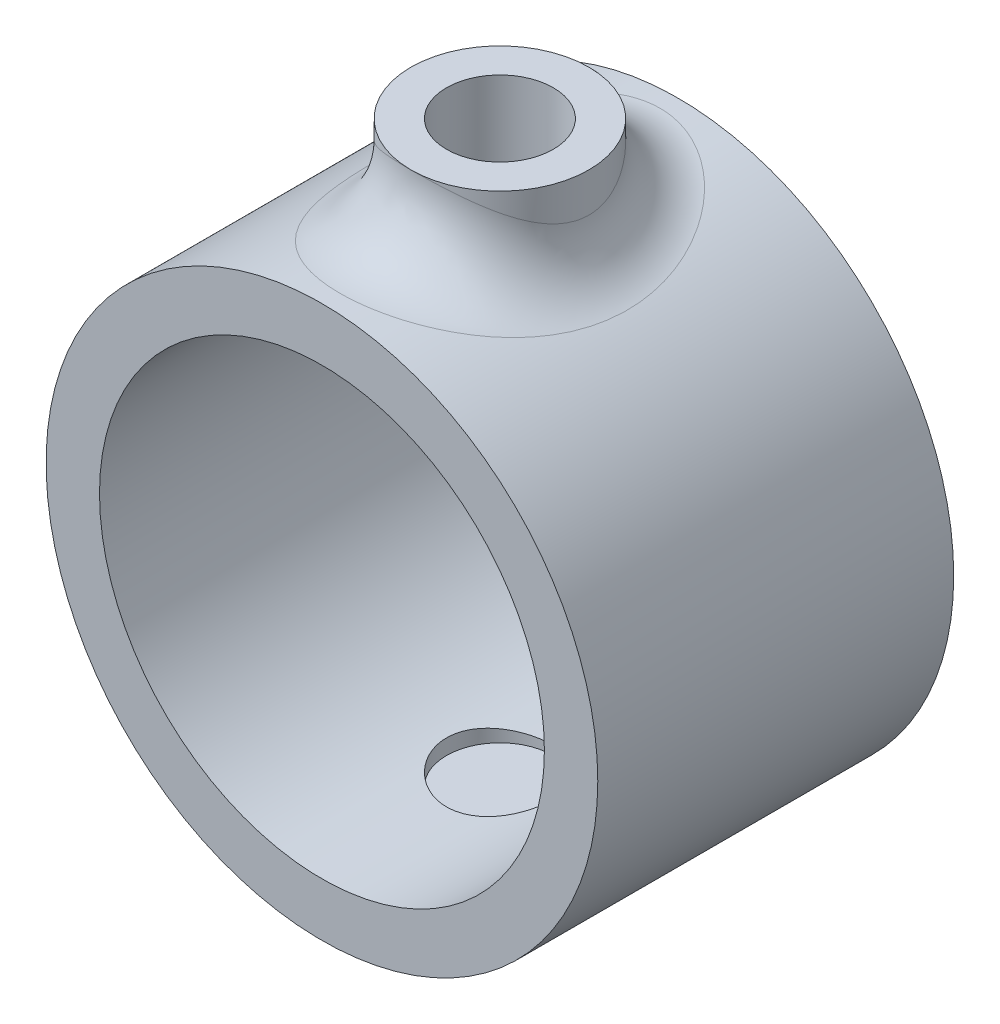
SolidWorks part; units mm, degrees
ref_plane "Front Plane" through (0, 0, 0) normal (0, 0, 1) x (1, 0, 0)
ref_plane "Top Plane" through (0, 0, 0) normal (0, 1, 0) x (1, 0, 0)
ref_plane "Right Plane" through (0, 0, 0) normal (1, 0, 0) x (0, 0, -1)
sketch "Sketch1" plane through (0, 0, 0) normal (0, 0, 1) x (1, 0, 0)
  circle A0 centre (0, 0) radius 6.25
  circle A1 centre (0, 0) radius 7.75
  dimension "D1" = 12.5
  dimension "D2" = 15.5
extrude "Boss-Extrude1" add sketch "Sketch1" along normal blind 5 and the other way blind 5
sketch "Sketch2" plane through (0, 0, 0) normal (0, 1, 0) x (1, 0, 0)
  circle A0 centre (0, 0) radius 1.5
  dimension "D1" = 3
extrude "Cut-Extrude1" cut sketch "Sketch2" against normal blind 6.5 and the other way blind 40
ref_plane "Plane1" through (0, 7.75, 0) normal (0, 1, 0) x (1, 0, 0)
sketch "Sketch3" plane through (0, 7.75, 0) normal (0, 1, 0) x (1, 0, 0)
  circle A0 centre (0, 0) radius 2.5
  circle A1 centre (0, 0) radius 1.5
  dimension "D1" = 5
  dimension "D2" = 3
extrude "Boss-Extrude2" add sketch "Sketch3" along normal blind 2 and the other way blind 1
fillet "Fillet2" radius 2 1 edges at (-0.434, 7.7378, -2.462)
